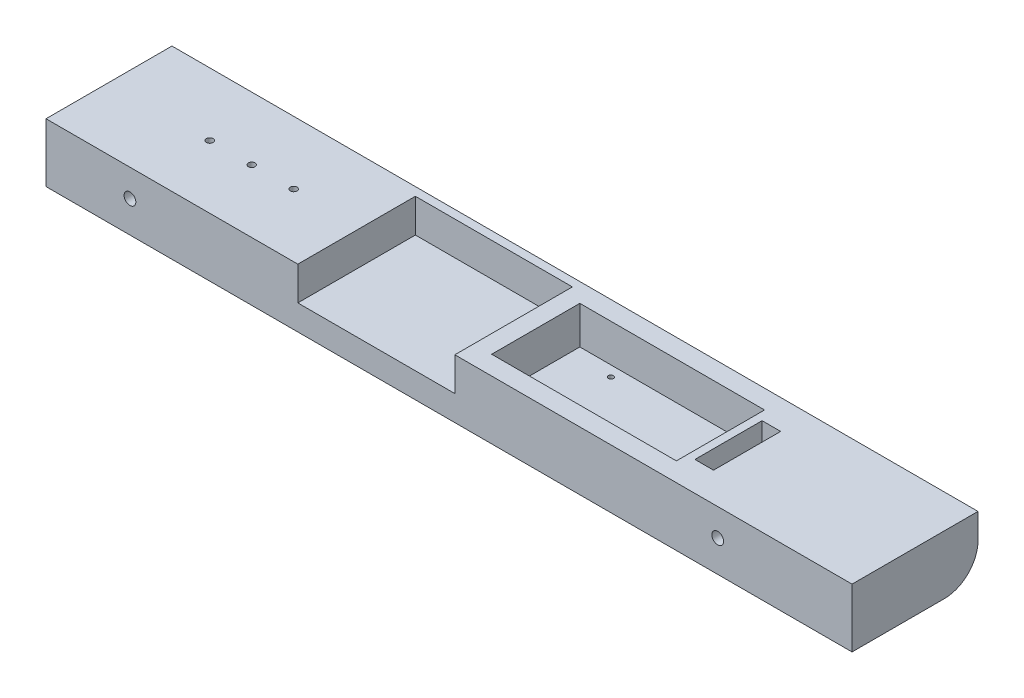
SolidWorks part; units mm, degrees
ref_plane "Front Plane" through (0, 0, 0) normal (0, 0, 1) x (1, 0, 0)
ref_plane "Top Plane" through (0, 0, 0) normal (0, 1, 0) x (1, 0, 0)
ref_plane "Right Plane" through (0, 0, 0) normal (1, 0, 0) x (0, 0, -1)
sketch "Sketch1" plane through (0, 0, 0) normal (1, 0, 0) x (0, 0, -1)
  line L1 (0, 0) -> (38.1, 0)
  line L2 (0, 0) -> (0, -17.78)
  line L3 (0, -17.78) -> (38.1, -17.78)
  line L4 (38.1, 0) -> (38.1, -17.78)
  dimension "D1" = 17.78
  dimension "D2" = 38.1
extrude "Boss-Extrude1" add sketch "Sketch1" along normal blind 243.84
sketch "Sketch2" plane through (0, 0, 0) normal (0, 1, 0) x (1, 0, 0)
  line L0 (243.84, 38.1) -> (243.84, 0) construction
  line L1 (129.1041, 32.385) -> (184.9841, 32.385)
  line L2 (129.1041, 32.385) -> (129.1041, 5.715)
  line L3 (129.1041, 5.715) -> (184.9841, 5.715)
  line L4 (184.9841, 32.385) -> (184.9841, 5.715)
  point P6 (243.84, 19.05)
  point P7 (184.9841, 19.05)
  dimension "D1" = 55.88
  dimension "D2" = 26.67
extrude "Cut-Extrude1" cut sketch "Sketch2" against normal blind 11.43
sketch "Sketch3" plane through (0, 0, 0) normal (0, 1, 0) x (1, 0, 0)
  line L1 (76.1779, 0) -> (123.6759, 0)
  line L2 (76.1779, 0) -> (76.1779, 35.56)
  line L3 (76.1779, 35.56) -> (123.6759, 35.56)
  line L4 (123.6759, 0) -> (123.6759, 35.56)
  line L7 (243.84, 0) -> (0, 0) construction
  dimension "D1" = 47.498
  dimension "D2" = 35.56
extrude "Cut-Extrude2" cut sketch "Sketch3" against normal blind 10.16
sketch "Sketch4" plane through (0, 0, 0) normal (0, 0, 1) x (1, 0, 0)
  circle A0 centre (25.4, -8.255) radius 1.778
  circle A1 centre (203.2, -8.255) radius 1.778
  dimension "D1" = 3.556
extrude "Cut-Extrude3" cut sketch "Sketch4" against normal blind 25.4
sketch "Sketch5" plane through (0, 0, 0) normal (0, 1, 0) x (1, 0, 0)
  line L0 (0, 38.1) -> (0, 0) construction
  circle A0 centre (55.88, 19.05) radius 1.016
  point P4 (0, 19.05)
  dimension "D2" = 2.032
  dimension "D1" = 55.88
extrude "Cut-Extrude4" cut sketch "Sketch5" against normal blind 10.16
sketch "Sketch6" plane through (0, 0, 0) normal (0, 1, 0) x (1, 0, 0)
  line L0 (200.66, 8.89) -> (200.66, 29.21) construction
  line L1 (243.84, 38.1) -> (243.84, 0) construction
  circle A0 centre (200.66, 29.21) radius 0.762
  circle A1 centre (200.66, 8.89) radius 0.762
  point P4 (200.66, 19.05)
  point P7 (243.84, 19.05)
  dimension "D2" = 1.524
  dimension "D1" = 43.18
  dimension "D3" = 20.32
extrude "Cut-Extrude5" cut sketch "Sketch6" against normal blind 6.35
pattern_linear "LPattern1" count 2 spacing 38.1 along (1, 0, 0) of "Cut-Extrude5"
pattern_linear "LPattern2" count 3 spacing 12.7 along (-1, 0, 0) of "Cut-Extrude4"
ref_plane "Plane1" through (0, -8.89, 0) normal (0, 1, 0) x (1, 0, 0)
mirror "Mirror2" about plane through (0, -8.89, 0) normal (0, 1, 0) of "LPattern1"
sketch "Sketch7" plane through (0, -17.78, 0) normal (0, -1, 0) x (1, 0, 0)
  line L0 (243.84, 0) -> (243.84, -38.1) construction
  line L1 (187.4135, -8.89) -> (193.04, -8.89)
  line L2 (187.4135, -8.89) -> (187.4135, -29.21)
  line L3 (187.4135, -29.21) -> (193.04, -29.21)
  line L4 (193.04, -8.89) -> (193.04, -29.21)
  line L5 (200.66, -29.21) -> (238.76, -29.21) construction
  point P6 (243.84, -19.05)
  point P7 (193.04, -19.05)
  dimension "D1" = 50.8
extrude "Cut-Extrude6" cut sketch "Sketch7" against normal through all
ref_plane "Plane2" through (190.2268, 0, 0) normal (1, 0, 0) x (0, 0, -1)
mirror "Mirror3" about plane through (190.2268, 0, 0) normal (1, 0, 0) of "Mirror2"
sketch "Sketch8" plane through (0, -17.78, 0) normal (0, -1, 0) x (1, 0, 0)
  circle A0 centre (200.66, -8.89) radius 0.762
  circle A1 centre (238.76, -8.89) radius 0.762
  circle A2 centre (238.76, -29.21) radius 0.762
  circle A3 centre (200.66, -29.21) radius 0.762
  dimension "D1" = 2
  dimension "D2" = 2
extrude "Boss-Extrude2" add sketch "Sketch8" against normal up to surface (17.78 mm away) up to face at (190.2268, 0, -19.05)
fillet "Fillet1" radius 10.16 1 edges at (121.92, -17.78, -38.1)
sketch "Sketch10" plane through (0, -17.78, 0) normal (0, -1, 0) x (1, 0, 0)
  line L0 (141.6935, -8.89) -> (160.7435, -8.89) construction
  point P6 (175.2701, -8.89)
  dimension "D1" = 19.05
ref_plane "Plane3" through (160.7435, 0, 0) normal (1, 0, 0) x (0, 0, -1)
sketch "Sketch11" plane through (160.7435, 0, 0) normal (1, 0, 0) x (0, 0, -1)
  line L0 (27.94, -17.78) -> (38.1, -17.78)
  line L1 (38.1, -17.78) -> (38.1, -7.62)
  line L2 (38.1, -7.62) -> (38.1, 0) construction
  arc A0 (27.94, -17.78) -> (38.1, -7.62) centre (27.94, -7.62) ccw construction
  arc A1 (27.94, -17.78) -> (38.1, -7.62) centre (27.94, -7.62) ccw
  point P3 (36.1895, -17.78)
  point P9 (38.1, -17.78)
  point P10 (0, 0)
  point P13 (0, 0)
  point P14 (0, 0)
extrude "Boss-Extrude3" add sketch "Sketch11" along normal mid plane 41.91
sketch "Sketch12" plane through (0, -11.43, 0) normal (0, 1, 0) x (1, 0, 0)
  circle A0 centre (141.6935, 29.21) radius 0.762
  circle A1 centre (179.7935, 29.21) radius 0.762
extrude "Cut-Extrude8" cut sketch "Sketch12" against normal through all
fillet "Fillet2" radius 6.35 1 edges at (160.7435, -17.78, -38.1)
